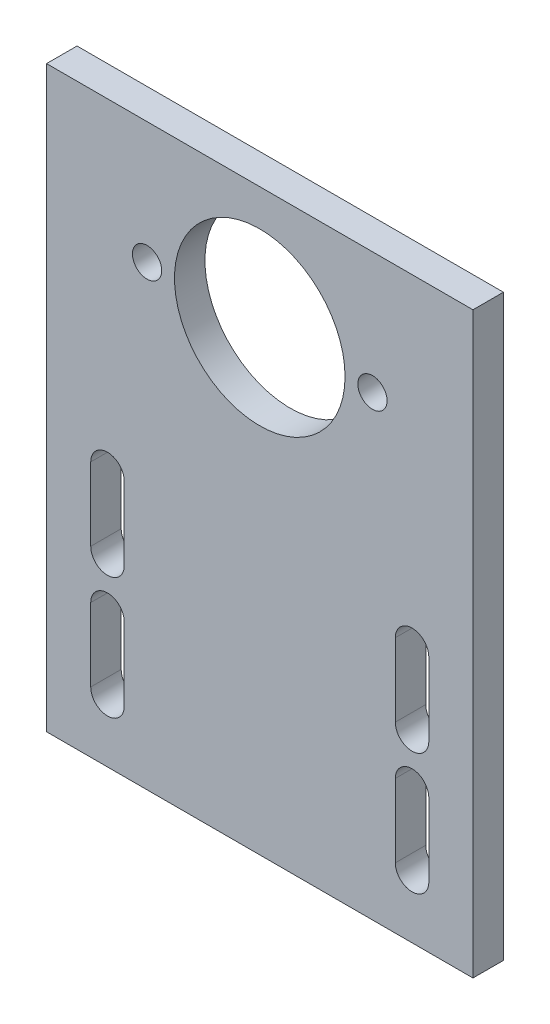
SolidWorks part; units mm, degrees
ref_plane "Front Plane" through (0, 0, 0) normal (0, 0, 1) x (1, 0, 0)
ref_plane "Top Plane" through (0, 0, 0) normal (0, 1, 0) x (1, 0, 0)
ref_plane "Right Plane" through (0, 0, 0) normal (1, 0, 0) x (0, 0, -1)
sketch "Sketch1" plane through (0, 0, 0) normal (0, 0, 1) x (1, 0, 0)
  line L0 (0, 0) -> (0, 100) construction
  line L1 (-35, -15) -> (35, -15) construction
  line L2 (-35, -15) -> (-35, 100)
  line L3 (-35, 100) -> (35, 100)
  line L4 (35, -15) -> (35, 100)
  line L5 (-35, -15) -> (35, 100) construction
  line L6 (-35, 100) -> (35, -15) construction
  line L7 (-18.5, 40) -> (18.5, 40) construction
  line L8 (0, 0) -> (0, -15) construction
  line L9 (-25, -5) -> (25, -5) construction
  line L10 (-35, -15) -> (-35, -35)
  line L11 (-25, -5) -> (-25, 7) construction
  line L12 (-35, -35) -> (35, -35)
  line L13 (35, -35) -> (35, -15)
  line L14 (-27.75, -5) -> (-27.75, 7)
  line L15 (-22.25, -5) -> (-22.25, 7)
  line L16 (25, -5) -> (25, 7) construction
  line L17 (27.75, -5) -> (27.75, 7)
  line L18 (22.25, -5) -> (22.25, 7)
  line L19 (-25, -25) -> (-25, -13) construction
  line L20 (-27.75, -25) -> (-27.75, -13)
  line L21 (-22.25, -25) -> (-22.25, -13)
  line L22 (25, -25) -> (25, -13) construction
  line L23 (27.75, -25) -> (27.75, -13)
  line L24 (22.25, -25) -> (22.25, -13)
  line L25 (-35, 60) -> (35, 60)
  circle A0 centre (-18.5, 40) radius 2.4
  circle A1 centre (18.5, 40) radius 2.4
  circle A2 centre (0, 40) radius 5
  circle A3 centre (-25, -5) radius 2.75 construction
  circle A4 centre (25, -5) radius 2.75 construction
  circle A5 centre (25, -25) radius 2.75 construction
  circle A6 centre (-25, -25) radius 2.75 construction
  circle A7 centre (0, 40) radius 14
  arc A8 (-27.75, -5) -> (-22.25, -5) centre (-25, -5) ccw
  arc A9 (-22.25, 7) -> (-27.75, 7) centre (-25, 7) ccw
  arc A10 (27.75, -5) -> (22.25, -5) centre (25, -5) cw
  arc A11 (22.25, 7) -> (27.75, 7) centre (25, 7) cw
  circle A12 centre (25, -5) radius 2.75 construction
  arc A13 (-27.75, -25) -> (-22.25, -25) centre (-25, -25) ccw
  arc A14 (-22.25, -13) -> (-27.75, -13) centre (-25, -13) ccw
  arc A15 (27.75, -25) -> (22.25, -25) centre (25, -25) cw
  arc A16 (22.25, -13) -> (27.75, -13) centre (25, -13) cw
  circle A17 centre (25, -25) radius 2.75 construction
  point P0 (0, 42.5)
  point P5 (-25, 1)
  point P10 (0, 40)
  point P18 (0, -5)
  point P34 (25, 1)
  point P41 (-25, -19)
  point P48 (25, -19)
  dimension "D4" = 4.8
  dimension "D5" = 10
  dimension "D6" = 5.5
  dimension "D11" = 28
  dimension "D14" = 2.75
  dimension "D15" = 2.75
  dimension "D1" = 70
  dimension "D2" = 115
  dimension "D3" = 37
  dimension "D7" = 10
  dimension "D8" = 60
  dimension "D9" = 10
  dimension "D10" = 20
  dimension "D12" = 10
  dimension "D13" = 12
  dimension "D16" = 12
  dimension "D17" = 40
extrude "Boss-Extrude1" add sketch "Sketch1" along normal blind 5 contours L25 L2 L10 L12 L13 L4 A14 L21 A13 L20 A9 L15 A8 L14 A7 A1 A0 L18 A11 L17 A10 L24 A16 L23 A15 region at (0, 10.6895, 0)
